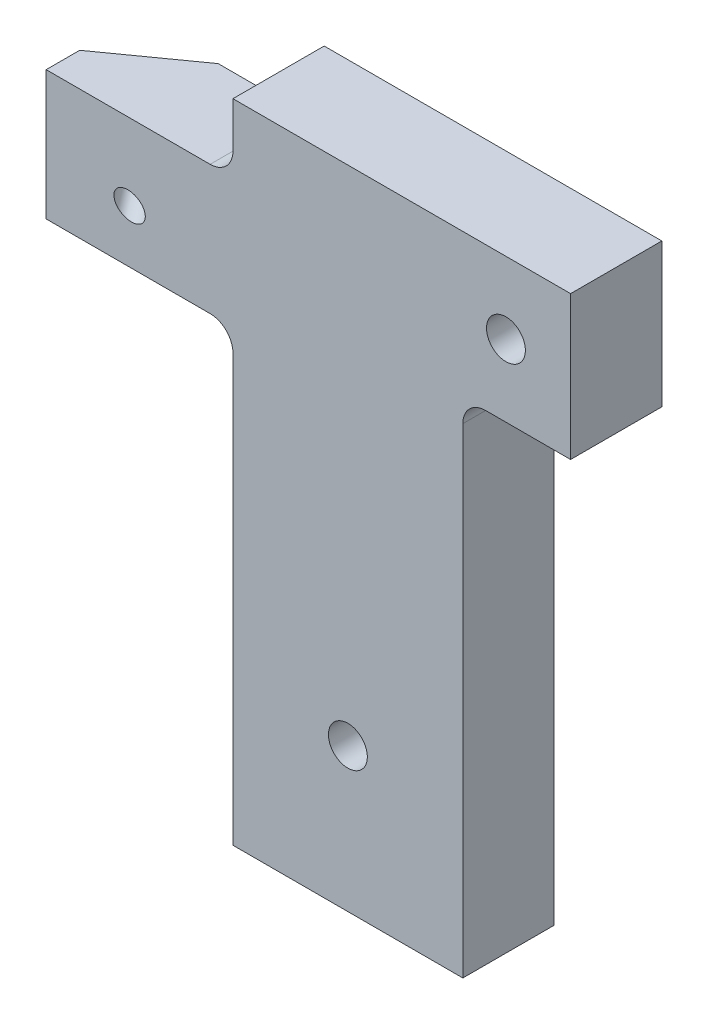
SolidWorks part; units mm, degrees
other "Markup1"
sketch "Sketch12" plane through (40, 0, 0) normal (0.1663, -0.0186, -0.9859) x (0.442, -0.8924, 0.0914)
material "6061-T4 (SS)"
ref_plane "Front Plane" through (0, 0, 0) normal (0, 0, 1) x (1, 0, 0)
ref_plane "Top Plane" through (0, 0, 0) normal (0, 1, 0) x (1, 0, 0)
ref_plane "Right Plane" through (0, 0, 0) normal (1, 0, 0) x (0, 0, -1)
sketch "Sketch1" plane through (0, 0, 0) normal (0, 0, 1) x (1, 0, 0)
  line L1 (0, 0) -> (36.5, 0)
  line L2 (0, 0) -> (0, 45)
  line L3 (0, 45) -> (36.5, 45)
  line L4 (36.5, 0) -> (36.5, 45)
  dimension "D1" = 36.5
  dimension "D2" = 45
extrude "Boss-Extrude1" add sketch "Sketch1" along normal blind 6.35
ref_plane "Plane1" through (-4.2162, 1.2018, -5.9041) normal (-0.5733, 0.1634, -0.8029) x (-0.8168, -0.1912, 0.5444)
sketch "Sketch4" plane through (-4.2162, 1.2018, -5.9041) normal (-0.5733, 0.1634, -0.8029) x (-0.8168, -0.1912, 0.5444)
  line L5 (16.3982, 68.5538) -> (-33.6018, 68.5538)
  line L6 (16.3982, 68.5538) -> (16.3982, 18.5538)
  line L7 (16.3982, 18.5538) -> (-33.6018, 18.5538)
  line L8 (-33.6018, 68.5538) -> (-33.6018, 18.5538)
  line L9 (16.3982, 68.5538) -> (-33.6018, 18.5538) construction
  line L10 (16.3982, 18.5538) -> (-33.6018, 68.5538) construction
  point P0 (-8.6018, 43.5538)
  dimension "D1" = 50
extrude "Cut-Extrude1" cut sketch "Sketch4" against normal blind 4 contours L8 L7 L6 L5
sketch "Sketch7" plane through (0, 0, 0) normal (0, 0, -1) x (-1, 0, 0)
  line L0 (-36.5, 45) -> (-6.9768, 45) construction
  line L1 (0, 0) -> (-13, 0)
  line L2 (0, 0) -> (0, 31.25)
  line L3 (0, 31.25) -> (-11.4125, 31.25)
  line L4 (-13, 0) -> (-13, 29.6625)
  line L5 (0, 0) -> (-36.5, 0) construction
  line L6 (-36.5, 0) -> (-29, 0)
  line L7 (-36.5, 0) -> (-36.5, 35)
  line L8 (-36.5, 35) -> (-30.5875, 35)
  line L9 (-29, 0) -> (-29, 33.4125)
  line L10 (-13, 45) -> (-13, 41.8375)
  line L11 (-36.5, 0) -> (-36.5, 45) construction
  line L12 (-11.4125, 40.25) -> (0, 40.25)
  line L13 (-29, -28) -> (-29, 23) construction
  line L14 (-13, -28) -> (-13, 18.8194) construction
  line L15 (0, 40.25) -> (0, 45)
  line L16 (0, 45) -> (-13, 45)
  arc A0 (-11.4125, 31.25) -> (-13, 29.6625) centre (-11.4125, 29.6625) ccw
  arc A1 (-30.5875, 35) -> (-29, 33.4125) centre (-30.5875, 33.4125) cw
  arc A2 (-13, 41.8375) -> (-11.4125, 40.25) centre (-11.4125, 41.8375) ccw
  point P9 (-13, 31.25)
  dimension "D2" = 1.5875
  dimension "D3" = 1.5875
  dimension "D6" = 1.5875
  dimension "D1" = 31.25
  dimension "D4" = 10
  dimension "D5" = 9
extrude "Cut-Extrude2" cut sketch "Sketch7" against normal blind 19
hole_wizard "#2-56 Tapped Hole1" positions "Sketch8" profile "Sketch9" tap size "#2-56" standard "ANSI Inch" end condition through all
sketch "Sketch8" plane through (-1.9229, 0.5481, -2.6927) normal (-0.5733, 0.1634, -0.8029) x (-0.8168, -0.1912, 0.5444)
  point P0 (-7.9669, 34.9918)
sketch "Sketch9" plane through (2.3271, 35.9382, 1.4759) normal (0.6651, 0.6651, -0.3396) x (-0.4785, 0.7287, 0.49)
  line L0 (0, 0) -> (0, 29.3787)
  line L1 (0, 29.3787) -> (0.889, 29.3787)
  line L2 (0.889, 29.3787) -> (0.889, 0)
  line L5 (0.889, 0) -> (0, 0)
  line L11 (0, -6.35) -> (0, 107.95) construction
  dimension "Thru Tap Drill Dia." = 1.778
  dimension "Thru Tap Drill Depth" = 29.3787
cosmetic thread "Hole Thread1" parameters "D2"=2.1844
hole_wizard "CBORE for #2 Socket Head Cap Screw1" positions "Sketch10" profile "Sketch11" counterbore size "#2" standard "ANSI Inch" end condition through all
sketch "Sketch10" plane through (0, 0, 0) normal (0, 0, -1) x (-1, 0, 0)
  point P0 (-21, 10)
  point P7 (-32, 40)
sketch "Sketch11" plane through (21, 10, 0) normal (1, 0, 0) x (0, 1, 0)
  line L0 (0, 0) -> (0, 6.35)
  line L1 (0, 6.35) -> (1.3525, 6.35)
  line L3 (1.3525, 6.35) -> (1.3525, 2.1844)
  line L4 (1.3525, 2.1844) -> (2.3812, 2.1844)
  line L5 (2.3812, 2.1844) -> (2.3812, 0)
  line L7 (2.3812, 0) -> (0, 0)
  line L11 (0, -6.35) -> (0, 107.95) construction
  dimension "Thru Hole Dia." = 2.7051
  dimension "Thru Hole Depth" = 6.35
  dimension "C'Bore Dia." = 4.7625
  dimension "C'Bore Depth" = 2.1844
